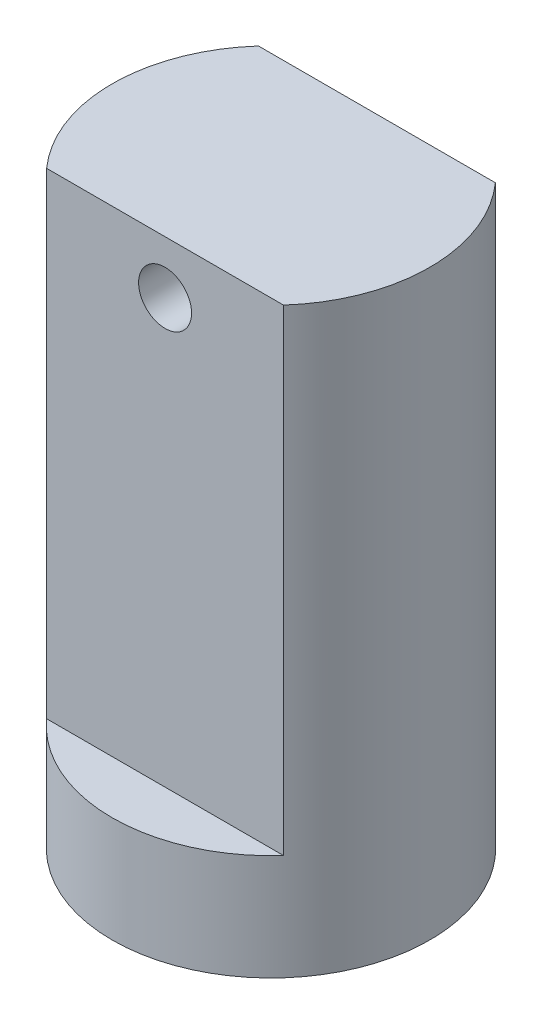
SolidWorks part; units mm, degrees
ref_plane "Front Plane" through (0, 0, 0) normal (0, 0, 1) x (1, 0, 0)
ref_plane "Top Plane" through (0, 0, 0) normal (0, 1, 0) x (1, 0, 0)
ref_plane "Right Plane" through (0, 0, 0) normal (1, 0, 0) x (0, 0, -1)
sketch "Sketch1" plane through (0, 0, 0) normal (0, 1, 0) x (1, 0, 0)
  circle A0 centre (0, 0) radius 38.1
  dimension "D1" = 76.2
extrude "Boss-Extrude1" add sketch "Sketch1" along normal blind 139.7
sketch "Sketch2" plane through (0, 0, 0) normal (0, -1, 0) x (1, 0, 0)
  circle A0 centre (0, 0) radius 6.35
  dimension "D1" = 12.7
extrude "Cut-Extrude1" cut sketch "Sketch2" against normal blind 25.4
sketch "Sketch3" plane through (0, 0, 0) normal (0, 0, 1) x (1, 0, 0)
  line L0 (38.1, 0) -> (38.1, 139.7) construction
  line L1 (-38.1, 139.7) -> (38.1, 139.7)
  line L2 (-38.1, 139.7) -> (-38.1, 25.4)
  line L3 (-38.1, 25.4) -> (38.1, 25.4)
  line L4 (38.1, 139.7) -> (38.1, 25.4)
  dimension "D1" = 114.3
extrude "Cut-Extrude2" cut sketch "Sketch3" along normal blind 25.4 from offset 25.4
extrude "Cut-Extrude3" cut sketch "Sketch3<2>" against normal blind 25.4 from offset 25.4 offset against normal yes
sketch "Sketch3<2>" plane through (0, 0, 0) normal (0, 0, 1) x (1, 0, 0) same geometry as "Sketch3"
sketch "Sketch4" plane through (0, 0, 25.4) normal (0, 0, 1) x (1, 0, 0)
  line L0 (-28.3981, 139.7) -> (28.3981, 139.7) construction
  circle A0 centre (0, 127) radius 6.35
  dimension "D2" = 12.7
  dimension "D1" = 12.7
extrude "Cut-Extrude4" cut sketch "Sketch4" against normal through all
